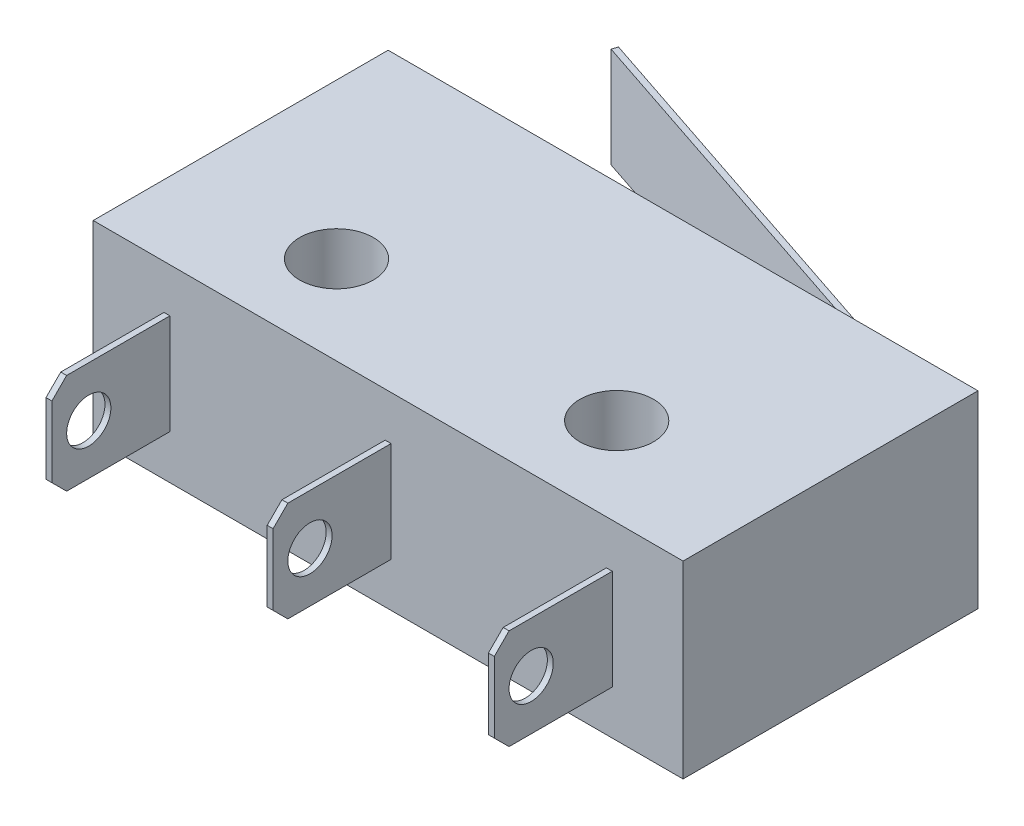
SolidWorks part; units mm, degrees
ref_plane "Front Plane" through (0, 0, 0) normal (0, 0, 1) x (1, 0, 0)
ref_plane "Top Plane" through (0, 0, 0) normal (0, 1, 0) x (1, 0, 0)
ref_plane "Right Plane" through (0, 0, 0) normal (1, 0, 0) x (0, 0, -1)
sketch "Sketch1" plane through (0, 0, 0) normal (0, 1, 0) x (1, 0, 0)
  line L0 (7.3, 5) -> (7.3, 5.5)
  line L1 (-10, 5) -> (10, 5)
  line L2 (-10, 5) -> (-10, -5)
  line L3 (-10, -5) -> (10, -5)
  line L4 (10, 5) -> (10, -5)
  line L5 (-10, 5) -> (10, -5) construction
  line L6 (-10, -5) -> (10, 5) construction
  line L7 (7.3, 5.5) -> (-7.688, 10.5)
  line L8 (7.1, 5) -> (7.1, 5.3559)
  line L9 (7.1, 5.3559) -> (-7.7513, 10.3103)
  line L10 (-7.688, 10.5) -> (-7.7513, 10.3103)
  line L11 (0, -5) -> (0, -2) construction
  line L12 (-6, -2) -> (6, -2) construction
  line L13 (7.6, -9) -> (7.4, -9)
  line L14 (7.6, -9) -> (7.6, -5)
  line L15 (7.4, -9) -> (7.4, -5)
  line L16 (0, -5) -> (0, -9) construction
  line L20 (-0.1, -5) -> (-0.1, -9)
  line L21 (0.1, -5) -> (0.1, -9)
  line L22 (-0.1, -9) -> (0.1, -9)
  line L23 (4.5, 5) -> (4.5, 5.5)
  line L24 (-0.1, -9) -> (-7.6, -9) construction
  line L25 (2.5, 5.5) -> (2.5, 5)
  line L26 (-7.6, -9) -> (-7.6, -5)
  line L27 (-7.4, -9) -> (-7.4, -5)
  line L28 (-7.6, -9) -> (-7.4, -9)
  circle A0 centre (-4.75, -2) radius 1.25
  circle A1 centre (4.75, -2) radius 1.25
  arc A2 (4.5, 5.5) -> (2.5, 5.5) centre (3.5, 5.5) ccw
  point P0 (0, 0)
  point P16 (0, -2)
  dimension "D8" = 2.5
  dimension "D9" = 2.5
  dimension "D17" = 2
  dimension "D20" = 1
  dimension "D1" = 10
  dimension "D2" = 20
  dimension "D3" = 0.5
  dimension "D4" = 15.8
  dimension "D5" = 5.5
  dimension "D7" = 12
  dimension "D10" = 3
  dimension "D11" = 2.7
  dimension "D12" = 4
  dimension "D18" = 5.5
  dimension "D19" = 0.5
  dimension "D21" = 7.5
  dimension "D6" = 0.2
  dimension "D13" = 0.1
  dimension "D14" = 0.1
  dimension "D22" = 0.2
extrude "Boss-Extrude1" add sketch "Sketch1" along normal blind 6.4 contours L4 L1 L2 L3 A1 A0 region at (0, 0, -0.1032)
extrude "Boss-Extrude2" add sketch "Sketch1<3>" along normal blind 3.4 from offset 1.5 contours L23 A2 L25 L1 | L7 L10 L9 L8 L1 L0 | L13 L3 | L20 L22 L21 L3 | L3 region at (-0.062, 0, -7.8451) region at (3.5, 0, -5.6621) region at (7.5, 0, 7) region at (0, 0, 7) region at (-7.5, 0, 7)
sketch "Sketch1<3>" plane through (0, 0, 0) normal (0, 1, 0) x (1, 0, 0) same geometry as "Sketch1"
chamfer "Chamfer2" distance 0.5 angle 45 6 edges at (7.5, 1.5, 9) (7.5, 4.9, 9) (0, 1.5, 9) (0, 4.9, 9) (-7.5, 1.5, 9) (-7.5, 4.9, 9)
sketch "Sketch3" plane through (-7.6, 0, 0) normal (-1, 0, 0) x (0, 0, 1)
  line L0 (9, 3.2) -> (8.5, 3.2) construction
  line L1 (9, 4.4) -> (9, 2) construction
  circle A0 centre (7.75, 3.2) radius 0.75
  dimension "D1" = 0.5
  dimension "D2" = 1.5
extrude "Cut-Extrude2" cut sketch "Sketch3" against normal blind 20.4
